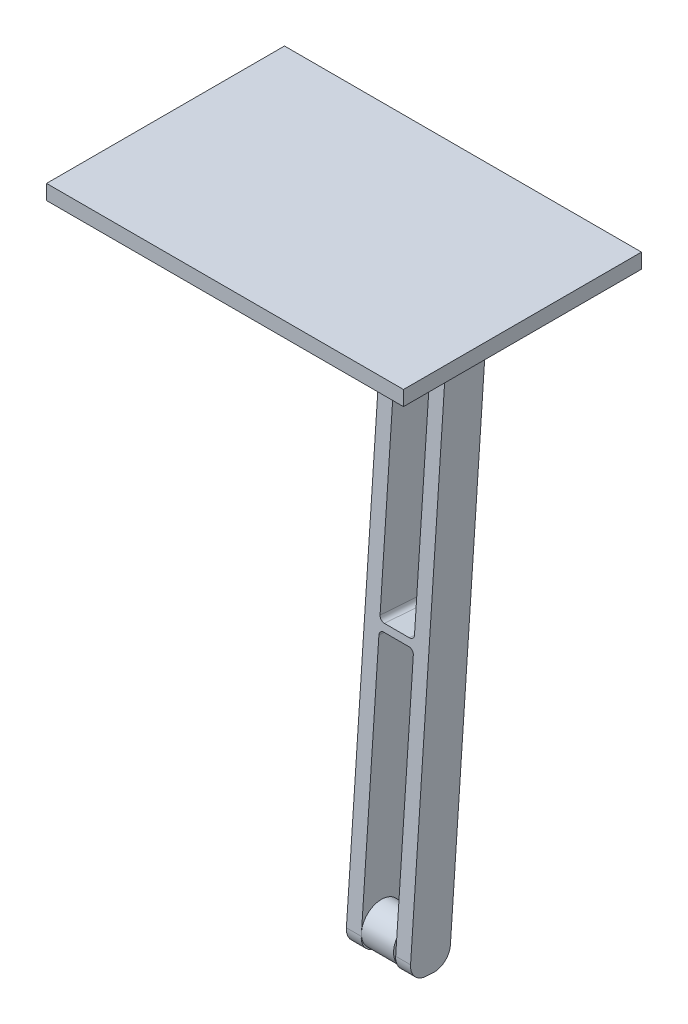
SolidWorks part; units mm, degrees
ref_plane "Front Plane" through (0, 0, 0) normal (0, 0, 1) x (1, 0, 0)
ref_plane "Top Plane" through (0, 0, 0) normal (0, 1, 0) x (1, 0, 0)
ref_plane "Right Plane" through (0, 0, 0) normal (1, 0, 0) x (0, 0, -1)
ref_axis "Axis1" through (-88.99, 0, 0) along (1, 0, 0)
ref_plane "Plane1" through (0, 0, 0) normal (0, 0.0698, 0.9976) x (1, 0, 0)
sketch "Sketch4" plane through (0, 0, 0) normal (0, 0, 1) x (1, 0, 0)
  line L1 (-38.1, 0) -> (38.1, 0)
  line L2 (-38.1, 0) -> (-38.1, 3.175)
  line L3 (-38.1, 3.175) -> (38.1, 3.175)
  line L4 (38.1, 0) -> (38.1, 3.175)
  dimension "D1" = 76.2
  dimension "D2" = 3.175
extrude "Boss-Extrude4" add sketch "Sketch4" along normal blind 50.8
sketch "Sketch5" plane through (0, 0, 0) normal (0, 0.0698, 0.9976) x (1, 0, 0)
  line L0 (-88.99, 0) -> (88.99, 0) construction
  line L1 (-6.8872, 0) -> (-3.7122, 0)
  line L2 (-6.8872, 0) -> (-6.8872, -139.7)
  line L3 (-6.8872, -139.7) -> (-3.7122, -139.7)
  line L4 (-3.7122, 0) -> (-3.7122, -139.7)
  line L5 (3.6378, 0) -> (6.8128, 0)
  line L6 (3.6378, 0) -> (3.6378, -139.7)
  line L7 (3.6378, -139.7) -> (6.8128, -139.7)
  line L8 (6.8128, 0) -> (6.8128, -139.7)
  line L10 (-3.7122, -28.5805) -> (3.6378, -28.5805)
  line L11 (-3.7122, -28.5805) -> (-3.7122, -30.168)
  line L12 (-3.7122, -30.168) -> (3.6378, -30.168)
  line L13 (3.6378, -28.5805) -> (3.6378, -30.168)
  line L14 (-3.7122, -79.6309) -> (3.6378, -79.6309)
  line L15 (-3.7122, -79.6309) -> (-3.7122, -81.2184)
  line L16 (-3.7122, -81.2184) -> (3.6378, -81.2184)
  line L17 (3.6378, -79.6309) -> (3.6378, -81.2184)
  dimension "D1" = 7.35
  dimension "D2" = 3.175
  dimension "D3" = 3.175
  dimension "D4" = 139.7
  dimension "D5" = 1.5875
  dimension "D6" = 1.5875
extrude "Boss-Extrude5" add sketch "Sketch5" along normal blind 8.525 contours L4 L12 L6 L10 | L4 L16 L6 L14 | L2 L3 L4 L1 | L8 L7 L6 L5 region at (-0.0372, -29.3027, 2.049) region at (-0.0372, -80.2288, 5.6101)
sketch "Sketch6" plane through (-3.7122, 0, 0) normal (1, 0, 0) x (0, 0, -1)
  line L1 (-18.2492, -138.765) -> (-9.745, -139.3597) construction
  line L2 (-18.2492, -138.765) -> (-14.1697, -80.4259) construction
  line L3 (-9.745, -139.3597) -> (-5.6655, -81.0206) construction
  circle A0 centre (-13.6998, -134.8102) radius 4.2625
extrude "Boss-Extrude6" add sketch "Sketch6" along normal blind 6.85
fillet "Fillet1" radius 1 14 edges at (6.8128, 0, 4.2729) (-6.8872, 0, 4.2729) (3.6378, 0, 4.2729) (-3.7122, 0, 4.2729) (5.2253, 0, 8.5458) (-5.2997, 0, 8.5458) (3.6378, -79.1396, 9.8069) (3.6378, -80.7233, 9.9176) (-3.7122, -80.7233, 9.9176) (-3.7122, -79.1396, 9.8069) (3.6378, -29.7972, 6.3565) (3.6378, -28.2136, 6.2458) (-3.7122, -28.2136, 6.2458) (-3.7122, -29.7972, 6.3565)
fillet "Fillet2" radius 3.54 4 edges at (5.2253, -138.765, 18.2492) (5.2253, -139.3597, 9.745) (-5.2997, -139.3597, 9.745) (-5.2997, -138.765, 18.2492)
